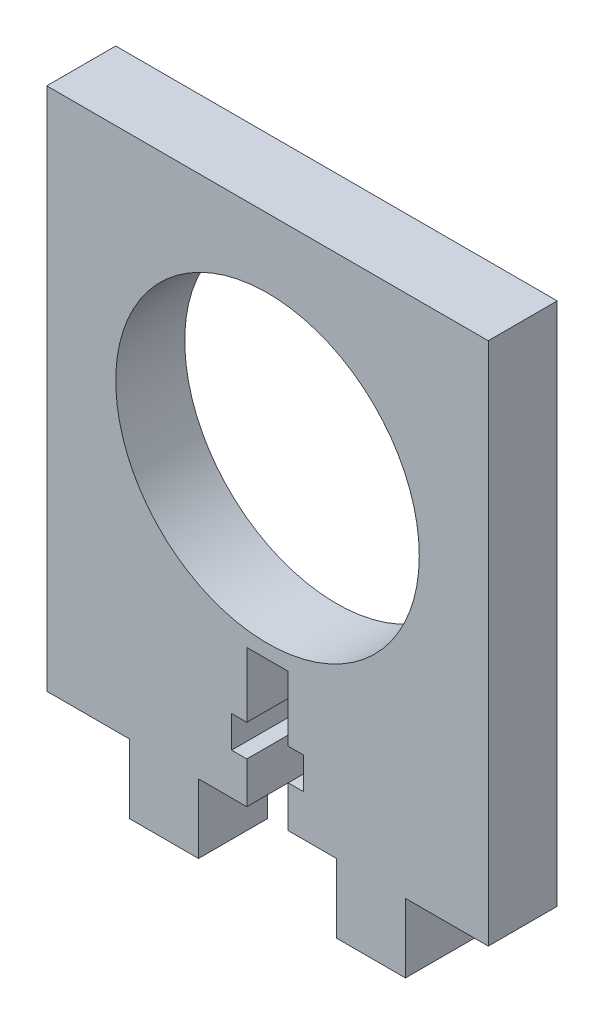
SolidWorks part; units mm, degrees
ref_plane "Front Plane" through (0, 0, 0) normal (0, 0, 1) x (1, 0, 0)
ref_plane "Top Plane" through (0, 0, 0) normal (0, 1, 0) x (1, 0, 0)
ref_plane "Right Plane" through (0, 0, 0) normal (1, 0, 0) x (0, 0, -1)
sketch "Sketch1" plane through (0, 0, 0) normal (0, 0, 1) x (1, 0, 0)
  line L0 (0, 0) -> (0, 27.0948) construction
  line L1 (-16, -22) -> (16, -22)
  line L2 (-16, -22) -> (-16, 16)
  line L3 (-16, 16) -> (16, 16)
  line L4 (16, -22) -> (16, 16)
  line L5 (-16, -22) -> (16, 16) construction
  line L6 (-16, 16) -> (16, -22) construction
  line L7 (0, 0) -> (37.5377, 0) construction
  circle A0 centre (0, 0) radius 11
  point P3 (0, -3)
  point P9 (0, 0)
  line B0 (-2.6, -19) -> (-2.6, -16.7)
  line B1 (1.5, -16.7) -> (1.5, -12)
  line B2 (-1.5, -12) -> (-1.5, -16.7)
  line B3 (-2.6, -16.7) -> (-1.5, -16.7)
  line B4 (0, -22) -> (0, -10.7792) construction
  line B5 (-1.5, -22) -> (-5, -22)
  line B6 (-5, -27) -> (-10, -27)
  line B7 (-10, -27) -> (-10, -22)
  line B8 (-5, -27) -> (-5, -22)
  line B9 (1.5, -22) -> (5, -22)
  line B10 (5, -22) -> (5, -27)
  line B11 (5, -27) -> (10, -27)
  line B12 (10, -27) -> (10, -22)
  line B13 (-1.5, -22) -> (1.5, -22) construction
  line B14 (1.5, -22) -> (1.5, -19)
  line B15 (1.5, -16.7) -> (2.6, -16.7)
  line B16 (2.6, -19) -> (1.5, -19)
  line B17 (1.5, -12) -> (-1.5, -12)
  line B18 (-1.5, -19) -> (-2.6, -19)
  line B19 (2.6, -16.7) -> (2.6, -19)
  line B20 (-1.5, -19) -> (-1.5, -22)
  line B21 (0, -12) -> (0, -22) construction
  dimension "D1" = 22
  dimension "D2" = 16
  dimension "D3" = 16
  dimension "D4" = 16
  dimension "D5" = 22
sketch_block_instance "Insert M3 plots ep 5mm-1"
sketch_block "Insert M3 plots ep 5mm" parameters "D1"=10, "D2"=5, "D3"=5
sketch_block_instance "Decoupe Insert M3-4"
sketch_block "Decoupe Insert M3" parameters "D1"=5.2, "D2"=3, "D3"=2.3, "D4"=3, "D5"=10
extrude "Boss-Extrude1" add sketch "Sketch1" along normal blind 5 contours L1 | L1 | L1 L4 L3 L2 A0 region at (-15.5032, -3, 0) region at (-7.5, -24.5, 0) region at (7.5, -24.5, 0)
